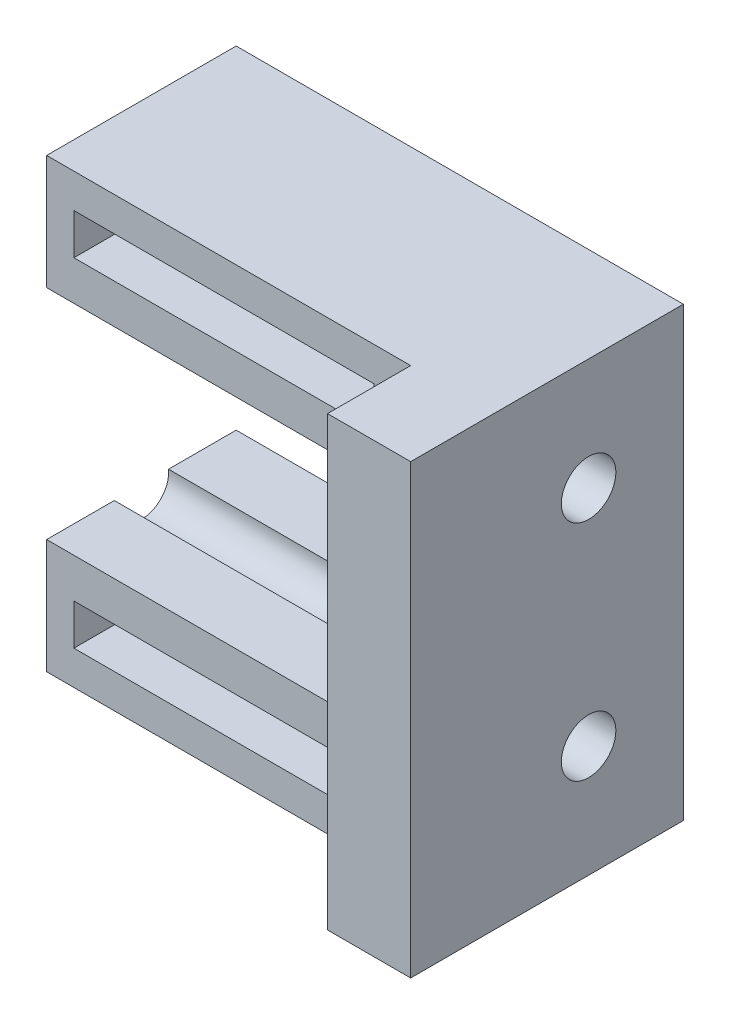
SolidWorks part; units mm, degrees
ref_plane "Front Plane" through (0, 0, 0) normal (0, 0, 1) x (1, 0, 0)
ref_plane "Top Plane" through (0, 0, 0) normal (0, 1, 0) x (1, 0, 0)
ref_plane "Right Plane" through (0, 0, 0) normal (1, 0, 0) x (0, 0, -1)
sketch "Sketch1" plane through (0, 0, 0) normal (0, 0, 1) x (1, 0, 0)
  line L0 (0, 0) -> (0, 18.0696) construction
  line L1 (-16.4, -16.4) -> (16.4, -16.4)
  line L2 (-16.4, -16.4) -> (-16.4, 16.4)
  line L3 (-16.4, 16.4) -> (16.4, 16.4)
  line L4 (16.4, -16.4) -> (16.4, 16.4)
  line L5 (-16.4, -16.4) -> (16.4, 16.4) construction
  line L6 (-16.4, 16.4) -> (16.4, -16.4) construction
  line L7 (16.4, 16.4) -> (10.3, 16.4)
  line L8 (16.4, 16.4) -> (16.4, -16.4)
  line L9 (16.4, -16.4) -> (10.3, -16.4)
  line L10 (10.3, 16.4) -> (10.3, -16.4)
  line L11 (-14.4, -10.9) -> (7.6, -10.9)
  line L12 (-14.4, -10.9) -> (-14.4, -13.9)
  line L13 (-14.4, -13.9) -> (7.6, -13.9)
  line L14 (7.6, -10.9) -> (7.6, -13.9)
  line L15 (-14.4, 13.9) -> (7.6, 13.9)
  line L16 (-14.4, 13.9) -> (-14.4, 10.9)
  line L17 (-14.4, 10.9) -> (7.6, 10.9)
  line L18 (7.6, 13.9) -> (7.6, 10.9)
  line L19 (-21.246, 0) -> (29.8315, 0) construction
  line L20 (-16.4, -8) -> (7.6, -8)
  line L21 (-16.4, -8) -> (-16.4, 8)
  line L22 (-16.4, 8) -> (7.6, 8)
  line L23 (7.6, -8) -> (7.6, 8)
  point P0 (0, 0)
  dimension "D1" = 32.8
  dimension "D2" = 32.8
  dimension "D3" = 32.8
  dimension "D4" = 6.1
  dimension "D5" = 2.5
  dimension "D6" = 2.5
  dimension "D7" = 3
  dimension "D8" = 3
  dimension "D9" = 22
  dimension "D10" = 22
  dimension "D11" = 2
  dimension "D12" = 2
  dimension "D13" = 16
extrude "Boss-Extrude1" add sketch "Sketch1" along normal blind 13.9 contours L10 L3 L2 L1 L23 L20 L21 L22 L11 L14 L13 L12 L15 L18 L17 L16 region at (-15.9771, -12.2, 0)
extrude "Boss-Extrude2" add sketch "Sketch1<3>" along normal blind 20 contours L3 L10 L1 L4 region at (13.35, 0, 0)
sketch "Sketch1<3>" plane through (0, 0, 0) normal (0, 0, 1) x (1, 0, 0) same geometry as "Sketch1"
sketch "Sketch2" plane through (16.4, 0, 0) normal (1, 0, 0) x (0, 0, -1)
  line L0 (-13.9, 16.4) -> (-13.9, -16.4)
  line L2 (-20, 16.4) -> (0, 16.4) construction
  line L3 (-20, -16.4) -> (0, -16.4) construction
  line L4 (0, -16.4) -> (0, 16.4) construction
  line L5 (-6.95, 16.4) -> (-6.95, -16.4) construction
  line L6 (-13.9, -8.2) -> (7.2887, -8.2) construction
  line L7 (1.394, 8.2) -> (-23.6547, 8.2) construction
  circle A0 centre (-6.95, 8.2) radius 2
  circle A1 centre (-6.95, -8.2) radius 2
  dimension "D5" = 4
  dimension "D6" = 4
  dimension "D1" = 13.9
  dimension "D2" = 6.95
  dimension "D3" = 8.2
  dimension "D4" = 8.2
extrude "Cut-Extrude1" cut sketch "Sketch2" against normal through all contours A0 | A1 region at (16.4, 8.2, 6.95) region at (16.4, -8.2, 6.95)
